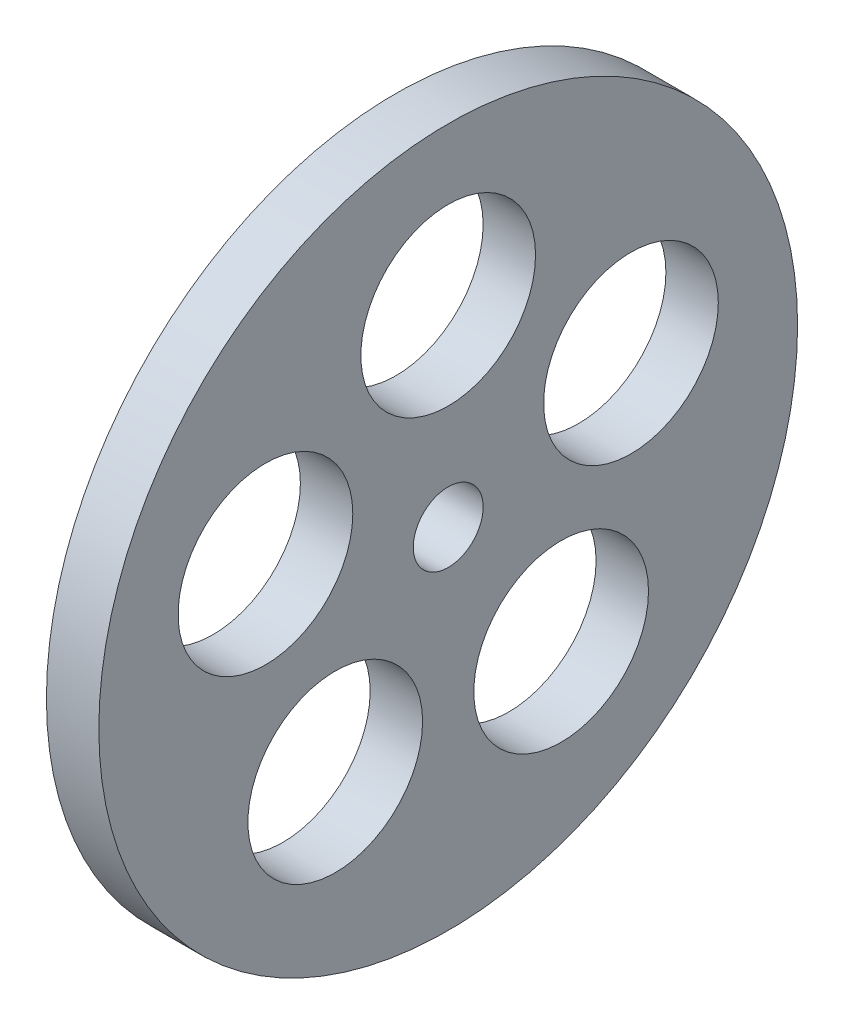
SolidWorks part; units mm, degrees
ref_plane "Front Plane" through (0, 0, 0) normal (0, 0, 1) x (1, 0, 0)
ref_plane "Top Plane" through (0, 0, 0) normal (0, 1, 0) x (1, 0, 0)
ref_plane "Right Plane" through (0, 0, 0) normal (1, 0, 0) x (0, 0, -1)
sketch "Sketch1" plane through (0, 0, 0) normal (1, 0, 0) x (0, 0, -1)
  line L0 (0, 4) -> (0, 40) construction
  circle A0 centre (0, 0) radius 40
  circle A1 centre (0, 0) radius 4
  circle A2 centre (0, 22) radius 10
  circle A3 centre (20.9232, 6.7984) radius 10
  circle A4 centre (12.9313, -17.7984) radius 10
  circle A5 centre (-12.9313, -17.7984) radius 10
  circle A6 centre (-20.9232, 6.7984) radius 10
  point P18 (0, 0)
  dimension "D1" = 80
  dimension "D2" = 8
  dimension "D3" = 20
  dimension "D4" = 5
extrude "Boss-Extrude1" add sketch "Sketch1" along normal blind 6
